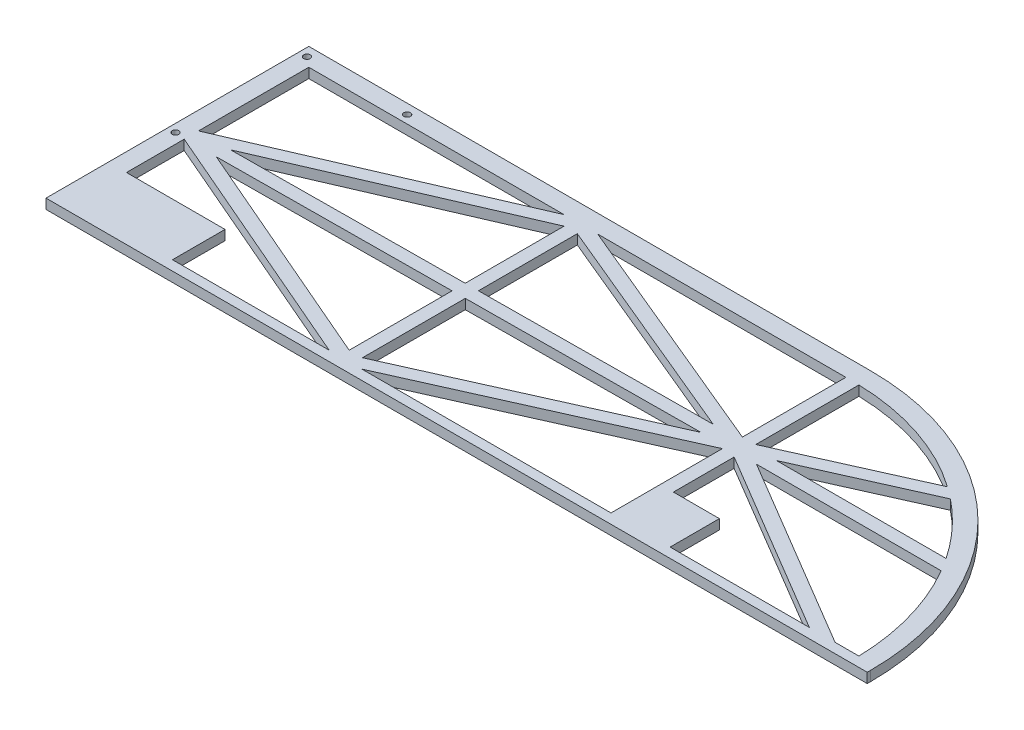
SolidWorks part; units mm, degrees
material "轻木"
ref_plane "前视基准面" through (0, 0, 0) normal (0, 0, 1) x (1, 0, 0)
ref_plane "上视基准面" through (0, 0, 0) normal (0, 1, 0) x (1, 0, 0)
ref_plane "右视基准面" through (0, 0, 0) normal (1, 0, 0) x (0, 0, -1)
other "Configuration Table"
sketch "草图1" plane through (0, 0, 0) normal (0, 1, 0) x (1, 0, 0)
  line L31 (-86.0578, 34) -> (-86.0578, 40) construction
  line L32 (-125, 40) -> (46, 40)
  line L37 (-125, 40) -> (-125, -40)
  line L60 (-125, -40) -> (125, -40)
  line L62 (125, -39) -> (125, -40)
  line L64 (-125, 40) -> (125, -40) construction
  line L72 (-125, -40) -> (125, 40) construction
  line L73 (-92.0578, 37) -> (-122.5578, 37) construction
  line L74 (-122.5578, 37) -> (-122.5578, -3) construction
  line L75 (-119.5578, -10) -> (-119.5578, 34) construction
  arc A5 (46, 40) -> (125, -39) centre (46, -39) cw
  circle A6 centre (-92.0578, 37) radius 1
  circle A7 centre (-122.5578, 37) radius 1
  circle A8 centre (-122.5578, -3) radius 1
  point P0 (0, 0)
  point P13 (-86.0578, 37)
  dimension "D3" = 79
  dimension "D4" = 2
  dimension "D1" = 80
  dimension "D2" = 250
  dimension "D9" = 3
  dimension "D5" = 6
  dimension "D6" = 40
  dimension "D7" = 2
  dimension "D8" = 2
extrude "凸台-拉伸1" add sketch "草图1" along normal blind 3 contours A5 L32 L37 L60 L62 A8 A7 A6 region at (-7.6522, 0, 1.6172)
sketch "草图4" plane through (0, 0, 0) normal (0, 1, 0) x (1, 0, 0)
  line L0 (46, 34.5) -> (-119.5, 34.5)
  line L1 (-119.5, 34.5) -> (-119.5, -37)
  line L2 (-119.5, -1.25) -> (46, 0) construction
  line L3 (46, 0) -> (-36.75, -37) construction
  line L4 (46, 37) -> (46, -37) construction
  line L5 (-36.75, -37) -> (-119.5, -1.25) construction
  line L8 (-119.5, -1.25) -> (-36.75, 34.5) construction
  line L9 (-36.75, 34.5) -> (46, 0) construction
  line L18 (-119.5, -37) -> (119.4728, -37)
  line L19 (46, 37) -> (-122, 37) construction
  line L20 (-122, 37) -> (-122, -37) construction
  line L21 (-36.75, 34.5) -> (-36.75, -37) construction
  line L22 (46, 0) -> (108.2997, 0) construction
  line L23 (46, 0) -> (108.2997, -37) construction
  line L24 (46, 0) -> (90.1681, 19.7489) construction
  line L25 (46.8164, -1.8258) -> (90.9845, 17.9231)
  line L26 (46, -2) -> (108.2997, -2)
  line L27 (44.9787, -1.7196) -> (104.383, -37)
  line L28 (-37.5196, 32.654) -> (45.2304, -1.846)
  line L29 (-119.4849, -3.2499) -> (46.0151, -1.9999)
  line L30 (45.1836, 1.8258) -> (-37.5664, -35.1742)
  line L31 (-38.75, 34.5) -> (-38.75, -37)
  line L32 (-118.7068, -3.086) -> (-35.9568, 32.664)
  line L33 (-35.9568, -35.164) -> (-118.7068, 0.586)
  line L34 (45.1836, 1.8258) -> (88.303, 21.1058)
  line L35 (46, 2) -> (108.2997, 2)
  line L36 (47.0213, 1.7196) -> (109.321, -35.2804)
  line L37 (-35.9804, 36.346) -> (46.7696, 1.846)
  line L38 (-119.5151, 0.7499) -> (45.9849, 1.9999)
  line L39 (46.8164, -1.8258) -> (-35.9336, -38.8258)
  line L40 (-34.75, 34.5) -> (-34.75, -37)
  line L41 (-120.2932, 0.586) -> (-37.5432, 36.336)
  line L42 (-37.5432, -38.836) -> (-120.2932, -3.086)
  line L43 (90.9845, 17.9231) -> (91.9589, 18.3588)
  line L48 (108.2997, -2) -> (109.5079, -2)
  line L49 (109.321, -35.2804) -> (112.2164, -37)
  line L50 (45.1836, 1.8258) -> (89.3517, 21.5747) construction
  line L51 (44.9787, -1.7196) -> (107.2784, -38.7196) construction
  line L52 (44, 37) -> (44, -37)
  line L53 (48, 37) -> (48, -37)
  line L55 (-119.5, -37) -> (-89.5, -37)
  line L56 (-119.5, -37) -> (-119.5, -21)
  line L57 (-119.5, -21) -> (-89.5, -21)
  line L58 (-89.5, -37) -> (-89.5, -21)
  line L59 (48, -37) -> (62, -37)
  line L60 (48, -37) -> (48, -22)
  line L61 (48, -22) -> (62, -22)
  line L62 (62, -37) -> (62, -22)
  arc A2 (119.4728, -37) -> (46, 34.5) centre (46, -39) ccw
  arc A11 (121.9737, -37) -> (46, 37) centre (46, -39) ccw construction
  point P17 (-36.75, -0.625)
  dimension "D3" = 2
  dimension "D5" = 2
  dimension "D7" = 30
  dimension "D9" = 14
  dimension "D10" = 15
  dimension "D8" = 16
  dimension "D4" = 2
  dimension "D6" = 2
extrude "切除-拉伸2" cut sketch "草图4" along normal blind 18 contours L1 L41 L0 | L32 L38 L31 | L33 L31 L29 | L58 L18 L42 L1 L57 | L29 L40 L30 | L28 L40 L38 | L52 L0 L37 | L52 L39 L18 | L34 A2 L53 | L35 A2 L43 L25 | L18 A2 L48 L26 L36 L49 | L62 L18 L27 L53 L61
